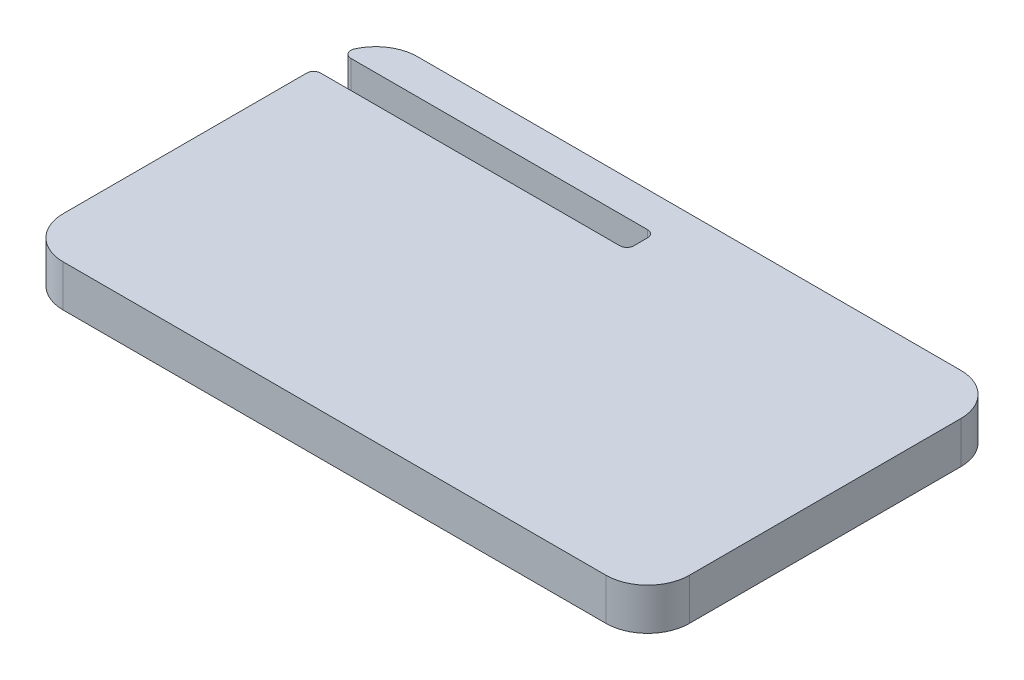
SolidWorks part; units mm, degrees
ref_plane "Alzado" through (0, 0, 0) normal (0, 0, 1) x (1, 0, 0)
ref_plane "Planta" through (0, 0, 0) normal (0, 1, 0) x (1, 0, 0)
ref_plane "Vista lateral" through (0, 0, 0) normal (1, 0, 0) x (0, 0, -1)
sketch "Croquis1" plane through (0, 0, 0) normal (0, 1, 0) x (1, 0, 0)
  line L5 (-22.5, 9.9298) -> (22.5, 9.9298)
  line L6 (-22.5, 9.9298) -> (-22.5, -15.5702)
  line L7 (-22.5, -15.5702) -> (22.5, -15.5702)
  line L8 (22.5, 9.9298) -> (22.5, -15.5702)
  dimension "D1" = 9.9298
  dimension "D2" = 22.5
  dimension "D3" = 25.5
  dimension "D4" = 45
extrude "Saliente-Extruir1" add sketch "Croquis1" along normal blind 3
sketch "Croquis2" plane through (0, 3, 0) normal (0, 1, 0) x (1, 0, 0)
  line L0 (-22.5, 9.9298) -> (-22.5, -15.5702) construction
  line L1 (-22.5, 7.4298) -> (0, 7.4298)
  line L2 (-22.5, 7.4298) -> (-22.5, 5.4298)
  line L3 (-22.5, 5.4298) -> (0, 5.4298)
  line L4 (0, 7.4298) -> (0, 5.4298)
  line L6 (22.5, 9.9298) -> (-22.5, 9.9298) construction
  dimension "D1" = 22.5
  dimension "D2" = 2.5
  dimension "D3" = 2
extrude "Cortar-Extruir1" cut sketch "Croquis2" against normal up to surface (3 mm away) up to face at (0, 0, 2.8202)
fillet "Redondeo1" radius 3 4 edges at (-22.5, 1.5, 15.5702) (-22.5, 1.5, -9.9298) (22.5, 1.5, 15.5702) (22.5, 1.5, -9.9298)
fillet "Redondeo4" radius 0.5 4 edges at (-22.5, 1.5, -5.4298) (0, 1.5, -5.4298) (0, 1.5, -7.4298) (-22.5, 1.5, -7.4298)
